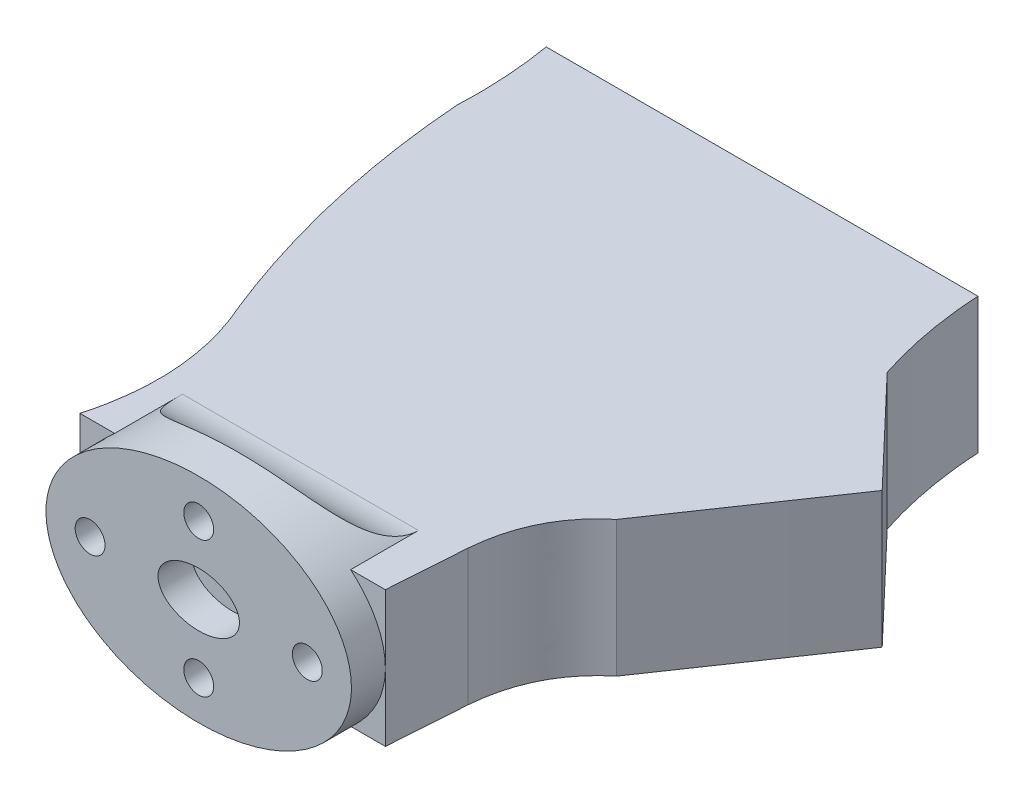
SolidWorks part; units mm, degrees
ref_plane "Plan de face" through (0, 0, 0) normal (0, 0, 1) x (1, 0, 0)
ref_plane "Plan de dessus" through (0, 0, 0) normal (0, 1, 0) x (1, 0, 0)
ref_plane "Plan de droite" through (0, 0, 0) normal (1, 0, 0) x (0, 0, -1)
sketch "Esquisse1" plane through (0, 0, 0) normal (0, 0, 1) x (1, 0, 0)
  ellipse E0 centre (0, 0) end of major axis (22.5, 0) minor radius 15.75
  point P1 (31.5, 0)
  point P8 (0, 0)
  dimension "D1" = 31.5
  dimension "D2" = 45
extrude "Boss.-Extru.1" add sketch "Esquisse1" along normal blind 5
hole_wizard "Dégagement M41" positions "Esquisse3" profile "Esquisse4" hole size "M4" standard "Ansi Metric"
sketch "Esquisse3" plane through (0, 0, 5) normal (0, 0, 1) x (1, 0, 0)
  point P0 (-16, 0)
  point P2 (16, 0)
  point P4 (0, 10)
  point P6 (0, -10)
  point P9 (0, 0)
  point P11 (0, 0)
  dimension "D1" = 10
  dimension "D2" = 10
  dimension "D3" = 16
  dimension "D4" = 16
sketch "Esquisse4" plane through (-16, 0, 5) normal (1, 0, 0) x (0, -1, 0)
  line L0 (0, 0) -> (0, 4.9)
  line L1 (0, 4.9) -> (2.2, 4.9)
  line L2 (2.2, 4.9) -> (2.2, 0)
  line L5 (2.2, 0) -> (0, 0)
  line L10 (0, 4.9) -> (-2.2, 4.9) construction
  line L11 (0, -6.35) -> (0, 107.95) construction
  dimension "Diamètre du perçage" = 4.4
  dimension "Profondeur du perçage" = 4.9
  dimension "Angle de pointe" = 180
sketch "Esquisse5" plane through (0, 0, 5) normal (0, 0, 1) x (1, 0, 0)
  ellipse E1 centre (0, 0) end of major axis (6, 0) minor radius 4
  point P0 (3.8981, 0.147)
  dimension "D1" = 8
  dimension "D2" = 12
extrude "Enlèv. mat.-Extru.1" cut sketch "Esquisse5" against normal blind 5
sketch "Esquisse6" plane through (0, 0, 0) normal (0, 1, 0) x (1, 0, 0)
  line L0 (6.2286, 231.7508) -> (238.2286, 231.7508) construction
  line L1 (-22.5, 0) -> (22.5, 0)
  line L2 (22.5, 0) -> (-22.5, 0) construction
  line L3 (22.5, 0) -> (23.2783, 11.4267)
  line L4 (46.429, 49.2579) -> (31.7325, 64.6938)
  line L5 (28.7078, 81.0958) -> (-34.9071, 81.0958)
  spline S0 degree 2 poles (23.2783, 11.4267) (24.051, 20.6657) (30.5639, 26.0011) knots 0 0 0 1 1 1
  spline S1 degree 2 poles (30.5639, 26.0011) (38.5083, 37.6214) (46.429, 49.2579) knots 0 0 0 1 1 1
  spline S2 degree 2 poles (31.7325, 64.6938) (29.137, 72.726) (28.7078, 81.0958) knots 0 0 0 1 1 1
  spline S3 degree 2 poles (-34.9071, 81.0958) (-33.7265, 74.1818) (-34.0589, 67.1712) knots 0 0 0 1 1 1
  spline S4 degree 2 poles (-34.0589, 67.1712) (-32.4639, 45.6471) (-24.446, 25.4681) knots 0 0 0 1 1 1
  spline S5 degree 2 poles (-24.446, 25.4681) (-18.8608, 13.0444) (-22.5, 0) knots 0 0 0 1 1 1
extrude "Boss.-Extru.3" add sketch "Esquisse6" along normal mid plane 20
fillet "Congé2" radius 10 2 edges at (0, 10, 0) (0, -10, 0)
